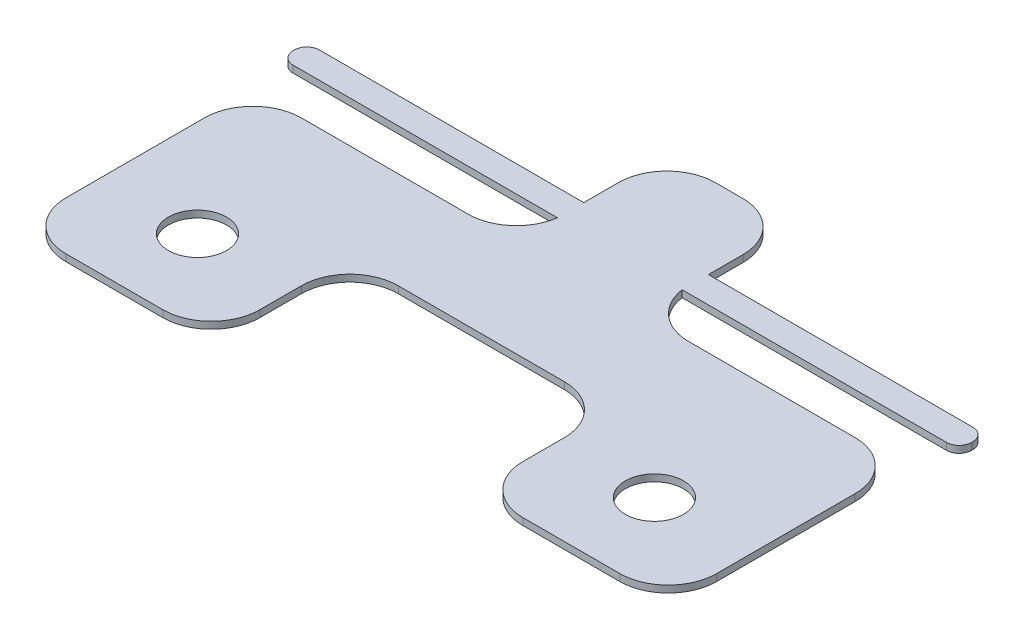
SolidWorks part; units mm, degrees
ref_plane "Front Plane" through (0, 0, 0) normal (0, 0, 1) x (1, 0, 0)
ref_plane "Top Plane" through (0, 0, 0) normal (0, 1, 0) x (1, 0, 0)
ref_plane "Right Plane" through (0, 0, 0) normal (1, 0, 0) x (0, 0, -1)
sketch "Sketch2" plane through (0, 0, 0) normal (0, 1, 0) x (1, 0, 0)
  line L0 (0, 0) -> (0, 35.8) construction
  line L1 (-9.5, 0) -> (9.5, 0)
  line L2 (9.5, 0) -> (9.5, -10)
  line L3 (9.5, -10) -> (23.5, -10)
  line L4 (23.5, -10) -> (23.5, 7)
  line L5 (23.5, 7) -> (4.5, 7)
  line L6 (4.5, 7) -> (4.5, 10)
  line L7 (4.5, 10) -> (24.5, 10)
  line L8 (24.5, 10) -> (24.5, 11.9)
  line L9 (24.5, 11.9) -> (4.5, 11.9)
  line L10 (4.5, 11.9) -> (4.5, 17.9)
  line L11 (4.5, 17.9) -> (-4.5, 17.9)
  line L12 (-4.5, 11.9) -> (-4.5, 17.9)
  line L13 (-24.5, 11.9) -> (-4.5, 11.9)
  line L14 (-24.5, 10) -> (-24.5, 11.9)
  line L15 (-4.5, 10) -> (-24.5, 10)
  line L16 (-4.5, 7) -> (-4.5, 10)
  line L17 (-23.5, 7) -> (-4.5, 7)
  line L18 (-23.5, -10) -> (-23.5, 7)
  line L19 (-9.5, -10) -> (-23.5, -10)
  line L20 (-9.5, 0) -> (-9.5, -10)
  circle A0 centre (16.5, -4) radius 2.1
  circle A1 centre (-16.5, -4) radius 2.1
  point P19 (0, 17.9)
  dimension "D11" = 4.2
  dimension "D12" = 6
  dimension "D13" = 7
  dimension "D1" = 6
  dimension "D2" = 10
  dimension "D3" = 1.9
  dimension "D4" = 20
  dimension "D5" = 19
  dimension "D6" = 9
  dimension "D7" = 9
  dimension "D8" = 3
  dimension "D9" = 14
  dimension "D10" = 10
sheet metal parameters "Sheet-Metal1" thickness 0.5 parameters "D1"=3.5
base flange "Base-Flange1" sketch "Sketch2" thickness 0.5 reverse thickness direction no parameters "D1"=3.5
fillet "Fillet1" radius 3.5 12 edges at (-23.5, -0.25, 10) (-9.5, -0.25, 10) (-9.5, -0.25, 0) (-23.5, -0.25, -7) (-4.5, -0.25, -7) (-4.5, -0.25, -17.9) (4.5, -0.25, -17.9) (4.5, -0.25, -7) (9.5, -0.25, 0) (9.5, -0.25, 10) (23.5, -0.25, 10) (23.5, -0.25, -7)
fillet "Fillet2" radius 0.9 4 edges at (-24.5, -0.25, -11.9) (-24.5, -0.25, -10) (24.5, -0.25, -11.9) (24.5, -0.25, -10)
sketch "Sketch3" plane through (0, 0, 0) normal (0, 1, 0) x (1, 0, 0)
  line L0 (4.75, 10.95) -> (0, 10.95) construction
  line L1 (0, 10.95) -> (-4.75, 10.95) construction
  line L2 (4.5, 10) -> (23.6, 10) construction
  line L3 (23.6, 11.9) -> (4.5, 11.9) construction
  point P0 (4.75, 10.95)
  point P1 (-4.75, 10.95)
  dimension "D1" = 0.95
  dimension "D2" = 0.95
  dimension "D3" = 9.5
flat pattern "Flat-Pattern1" [suppressed]
sketch "Bend-Lines1" plane through (0, 0, 0) normal (0, 1, 0) x (-1, 0, 0)
sketch3d "Bounding-Box1" [suppressed]
  line L0 (15, 0, 0) -> (-34, 0, 0) construction
  line L1 (15, -27.9, 0) -> (-34, -27.9, 0) construction
  line L2 (15, 0, 0) -> (15, -27.9, 0) construction
  line L3 (-34, 0, 0) -> (-34, -27.9, 0) construction
